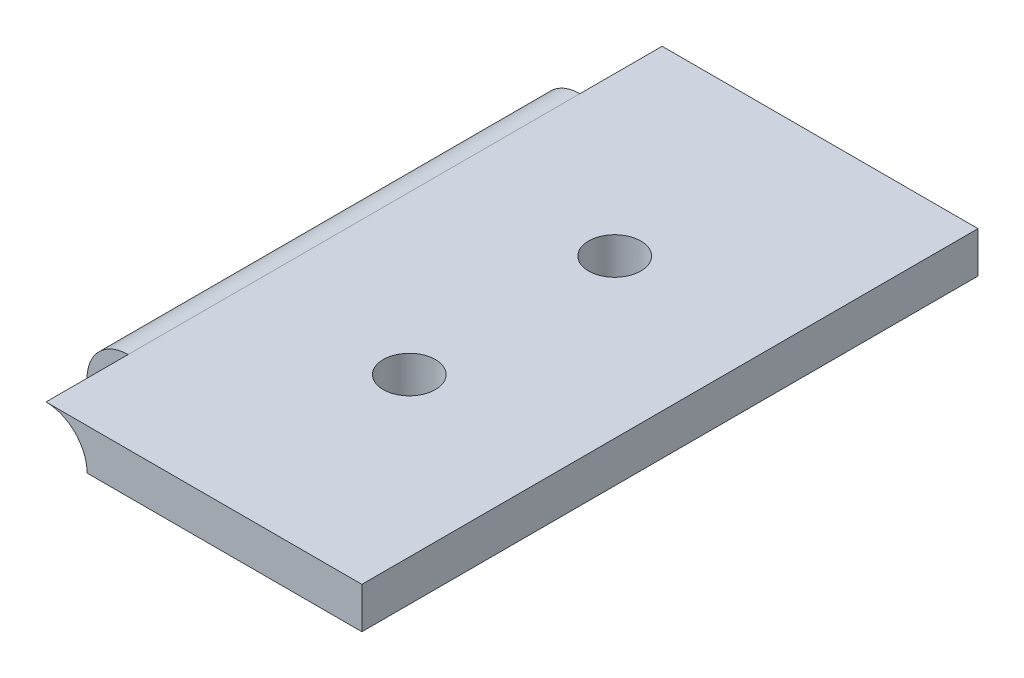
SolidWorks part; units mm, degrees
ref_plane "Front Plane" through (0, 0, 0) normal (0, 0, 1) x (1, 0, 0)
ref_plane "Top Plane" through (0, 0, 0) normal (0, 1, 0) x (1, 0, 0)
ref_plane "Right Plane" through (0, 0, 0) normal (1, 0, 0) x (0, 0, -1)
sketch "Sketch1" plane through (0, 0, 0) normal (0, 0, 1) x (1, 0, 0)
  line L0 (21.825, 0) -> (28.175, 0) construction
  line L1 (-98.5566, -165.7051) -> (0, 5) construction
  line L2 (0, 5) -> (270, 5) construction
  line L3 (21.825, 0) -> (28.175, 0)
  line L4 (-98.5566, -165.7051) -> (0, 5)
  line L5 (0, 5) -> (270, 5)
  line L6 (0, 0) -> (270, 0) construction
  line L7 (0, 0) -> (270, 0)
  line L8 (44.2265, 0) -> (5.7735, 0)
  line L9 (5.7735, 0) -> (5.7735, -5)
  line L10 (5.7735, -5) -> (44.2265, -5)
  line L11 (44.2265, -5) -> (44.2265, 0)
  line L12 (2.8868, 0) -> (-94.2265, -168.2051)
  line L13 (-98.5566, -165.7051) -> (-94.2265, -168.2051)
  line L14 (25, 0) -> (25, -5)
  circle A0 centre (5.7735, -5) radius 5
  circle A1 centre (5.7735, -5) radius 2.5
  point P13 (25, -5)
  point P14 (25, 0)
  point P19 (5.7735, 0)
  dimension "D4" = 10
  dimension "D5" = 5
  dimension "D1" = 120
  dimension "D2" = 5
  dimension "D3" = 5
extrude "Boss-Extrude1" add sketch "Sketch1" against normal blind 75 contours L10 L11 L8 L9
extrude "Boss-Extrude2" add sketch "Sketch1<4>" against normal blind 55 from offset 10 contours A1 L9 A0 L10 region at (5.6321, -1.25, 0) offset against normal yes
sketch "Sketch1<4>" plane through (0, 0, 0) normal (0, 0, 1) x (1, 0, 0) same geometry as "Sketch1"
sketch "Sketch5" plane through (0, -5, 0) normal (0, -1, 0) x (1, 0, 0)
  circle A0 centre (25, -25) radius 3.175 construction
  circle A1 centre (25, -50) radius 3.175 construction
  circle A2 centre (25, -25) radius 3.175
  circle A3 centre (25, -50) radius 3.175
extrude "Cut-Extrude8" cut sketch "Sketch5" against normal blind 55
extrude "Cut-Extrude9" cut sketch "Sketch1<14>" against normal blind 75 contours L10 A1 L9 region at (6.8345, -3.939, 0)
sketch "Sketch1<14>" plane through (0, 0, 0) normal (0, 0, 1) x (1, 0, 0) same geometry as "Sketch1"
extrude "Cut-Extrude10" cut sketch "Sketch1<15>" against normal blind 10 contours A1 L10 A0 L9 region at (8.2492, -2.5243, 0)
sketch "Sketch1<15>" plane through (0, 0, 0) normal (0, 0, 1) x (1, 0, 0) same geometry as "Sketch1"
extrude "Cut-Extrude11" cut sketch "Sketch1<16>" against normal blind 10 from offset 65 contours A1 L10 A0 L9 region at (8.2492, -2.5243, 0) offset against normal yes
sketch "Sketch1<16>" plane through (0, 0, 0) normal (0, 0, 1) x (1, 0, 0) same geometry as "Sketch1"
